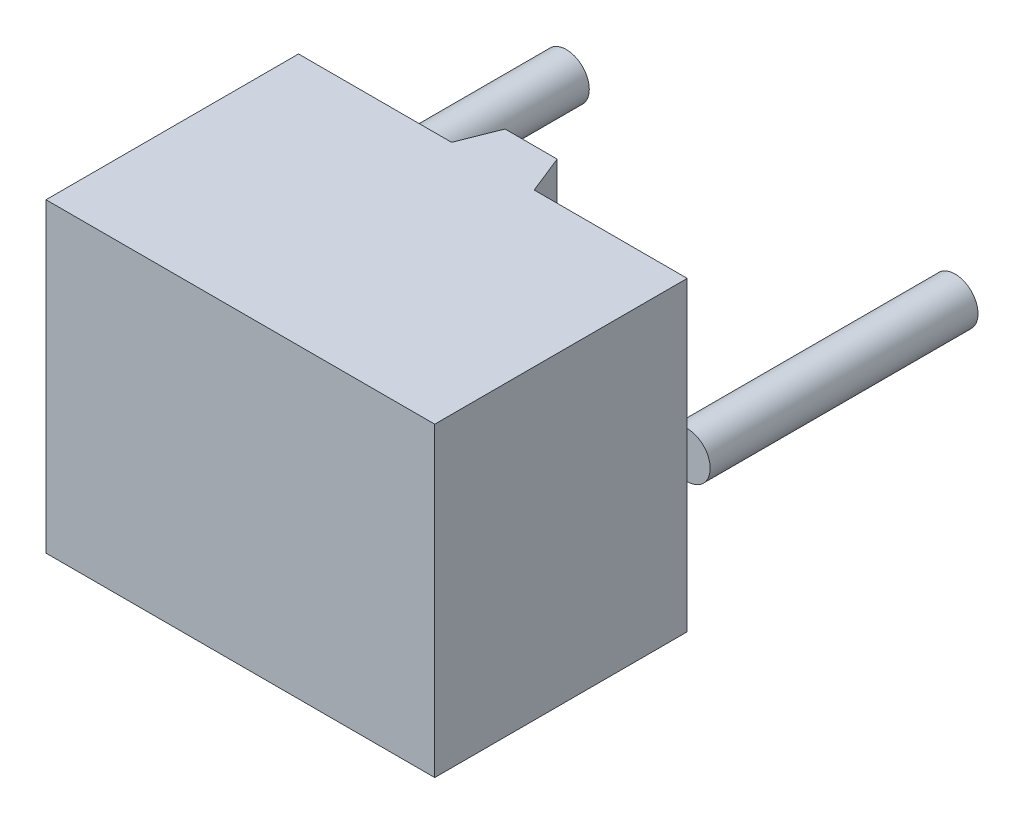
SolidWorks part; units mm, degrees
ref_plane "Front" through (0, 0, 0) normal (0, 0, 1) x (1, 0, 0)
ref_plane "Top" through (0, 0, 0) normal (0, 1, 0) x (1, 0, 0)
ref_plane "Right" through (0, 0, 0) normal (1, 0, 0) x (0, 0, -1)
sketch "Эскиз1" plane through (0, 0, 0) normal (0, 0, 1) x (1, 0, 0)
  line L1 (-0.8, -0.8) -> (0.8, -0.8)
  line L2 (-0.8, -0.8) -> (-0.8, 0.8)
  line L3 (-0.8, 0.8) -> (0.8, 0.8)
  line L4 (0.8, -0.8) -> (0.8, 0.8)
  line L5 (1.7, -0.8) -> (3.3, -0.8)
  line L6 (1.7, -0.8) -> (1.7, 0.8)
  line L7 (1.7, 0.8) -> (3.3, 0.8)
  line L8 (3.3, -0.8) -> (3.3, 0.8)
sketch "Эскиз2" plane through (0, 0, 0) normal (0, 0, 1) x (1, 0, 0)
  line L0 (2.54, -2) -> (0, -2)
  line L1 (2.54, 2) -> (0, 2)
  line L2 (0, 0) -> (0, 2)
  line L3 (5.08, 0) -> (5.08, 2)
  line L4 (0, -2) -> (0, 0)
  line L5 (5.08, -2) -> (5.08, 0)
  line L6 (5.08, -2) -> (2.54, -2)
  line L7 (5.08, 2) -> (2.54, 2)
  line L8 (0, 0) -> (5.08, 0) construction
  line L9 (2.54, 2) -> (2.54, -2) construction
  dimension "D1" = 5.08
  dimension "D2" = 4
  dimension "D3" = 2.54
extrude "Вытянуть1" add sketch "Эскиз2" along normal blind 3.8
sketch "Эскиз3" plane through (0, 2, 0) normal (0, 1, 0) x (-1, 0, 0)
  line L0 (0, 0) -> (0, 0.5)
  line L1 (0, 3.8) -> (0, 0) construction
  line L2 (0, 0.5) -> (-2, 0.5)
  line L3 (-2, 0.5) -> (-2.2, 0)
  line L4 (0.8, 0) -> (-0.8, 0) construction
  line L5 (-2.2, 0) -> (0, 0)
  line L6 (-2.54, 0) -> (-2.54, 1.5392) construction
  line L7 (-5.08, 0) -> (0, 0) construction
  line L8 (-2.88, 0) -> (-5.08, 0)
  line L9 (-3.08, 0.5) -> (-2.88, 0)
  line L10 (-5.08, 0.5) -> (-3.08, 0.5)
  line L11 (-5.08, 0) -> (-5.08, 0.5)
  dimension "D1" = 0.5
  dimension "D2" = 2
  dimension "D3" = 2.2
extrude "Вырез-Вытянуть1" cut sketch "Эскиз3" against normal blind 5.6
sketch "Эскиз4" plane through (0, 0, 0) normal (0, 0, 1) x (1, 0, 0)
  line L0 (2.54, 2) -> (2.54, -2) construction
  line L1 (2.88, 2) -> (2.2, 2) construction
  line L2 (2.2, -2) -> (2.88, -2) construction
  circle A0 centre (0, 0) radius 0.3
  circle A1 centre (5.08, 0) radius 0.3
  dimension "D1" = 0.6
extrude "Вытянуть2" add sketch "Эскиз4" against normal blind 3
extrude "Вытянуть3" add sketch "Эскиз4<2>" along normal up to surface (0.5 mm away) up to face at (4.08, 0, 0.5)
sketch "Эскиз4<2>" plane through (0, 0, 0) normal (0, 0, 1) x (1, 0, 0) same geometry as "Эскиз4"
